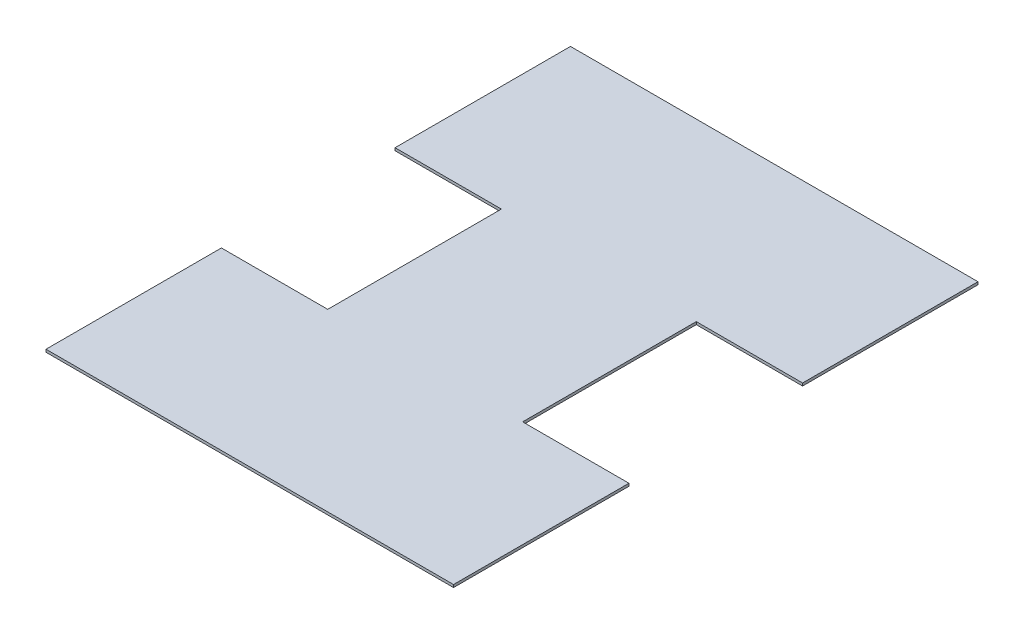
SolidWorks part; units mm, degrees
ref_plane "Front Plane" through (0, 0, 0) normal (0, 0, 1) x (1, 0, 0)
ref_plane "Top Plane" through (0, 0, 0) normal (0, 1, 0) x (1, 0, 0)
ref_plane "Right Plane" through (0, 0, 0) normal (1, 0, 0) x (0, 0, -1)
sketch "Sketch1" plane through (0, 0, 0) normal (0, 1, 0) x (1, 0, 0)
  line L0 (0, 296) -> (0, -296) construction
  line L1 (-230, -296) -> (230, -296)
  line L2 (-230, -296) -> (-230, -98)
  line L3 (-230, 296) -> (230, 296)
  line L4 (230, -296) -> (230, -98)
  line L5 (-230, -296) -> (230, 296) construction
  line L6 (-230, 296) -> (230, -296) construction
  line L7 (-230, 0) -> (230, 0) construction
  line L8 (-230, -98) -> (-110, -98)
  line L9 (-110, -98) -> (-110, 98)
  line L10 (-230, 98) -> (-110, 98)
  line L11 (230, -98) -> (110, -98)
  line L12 (110, -98) -> (110, 98)
  line L13 (230, 98) -> (110, 98)
  line L14 (230, 98) -> (230, 296)
  line L15 (-230, 98) -> (-230, 296)
  line L16 (230, 98) -> (230, -98) construction
  line L17 (-230, 98) -> (-230, -98) construction
  point P0 (0, 0)
  point P21 (-110, 0)
  dimension "D1" = 460
  dimension "D2" = 592
  dimension "D3" = 98
  dimension "D4" = 120
extrude "Boss-Extrude1" add sketch "Sketch1" along normal blind 3
sketch "Sketch2" plane through (0, 3, 0) normal (0, 1, 0) x (1, 0, 0)
  line L0 (188, -270) -> (200, -270) construction
  line L1 (188, -291) -> (200, -291) construction
  line L2 (188, -291) -> (188, -249) construction
  line L3 (188, -249) -> (200, -249) construction
  line L4 (200, -291) -> (200, -249) construction
  line L5 (188, -291) -> (200, -249) construction
  line L6 (188, -249) -> (200, -291) construction
  line L7 (0, 296) -> (0, -296) construction
  line L8 (230, 296) -> (-230, 296) construction
  line L9 (-230, -296) -> (230, -296) construction
  line L10 (-110, 0) -> (110, 0) construction
  line L11 (-110, 98) -> (-110, -98) construction
  line L12 (110, -98) -> (110, 98) construction
  line L13 (230, -296) -> (230, -98) construction
  line L14 (-188, -249) -> (-200, -291) construction
  line L15 (-188, -291) -> (-200, -249) construction
  line L16 (-200, -291) -> (-200, -249) construction
  line L17 (-188, -249) -> (-200, -249) construction
  line L18 (-188, -291) -> (-188, -249) construction
  line L19 (-188, -291) -> (-200, -291) construction
  line L20 (-188, -270) -> (-200, -270) construction
  line L21 (-188, 270) -> (-200, 270) construction
  line L22 (-188, 291) -> (-200, 291) construction
  line L23 (-188, 291) -> (-188, 249) construction
  line L24 (-188, 249) -> (-200, 249) construction
  line L25 (-200, 291) -> (-200, 249) construction
  line L26 (-188, 291) -> (-200, 249) construction
  line L27 (-188, 249) -> (-200, 291) construction
  line L28 (188, 249) -> (200, 291) construction
  line L29 (188, 291) -> (200, 249) construction
  line L30 (200, 291) -> (200, 249) construction
  line L31 (188, 249) -> (200, 249) construction
  line L32 (188, 291) -> (188, 249) construction
  line L33 (188, 291) -> (200, 291) construction
  line L34 (188, 270) -> (200, 270) construction
  line L35 (183.4, -233) -> (215, -233)
  line L36 (183.4, -233) -> (183.4, -103)
  line L37 (183.4, -103) -> (215, -103)
  line L38 (215, -233) -> (215, -103)
  line L39 (183.4, -233) -> (215, -103) construction
  line L40 (183.4, -103) -> (215, -233) construction
  line L41 (183.4, -168) -> (215, -168) construction
  line L42 (199.2, -103) -> (199.2, -233) construction
  line L43 (230, -98) -> (110, -98) construction
  line L44 (-199.2, -103) -> (-199.2, -233) construction
  line L45 (-183.4, -168) -> (-215, -168) construction
  line L46 (-183.4, -103) -> (-215, -233) construction
  line L47 (-183.4, -233) -> (-215, -103) construction
  line L48 (-215, -233) -> (-215, -103)
  line L49 (-183.4, -103) -> (-215, -103)
  line L50 (-183.4, -233) -> (-183.4, -103)
  line L51 (-183.4, -233) -> (-215, -233)
  line L52 (-183.4, 233) -> (-215, 103) construction
  line L53 (-183.4, 103) -> (-215, 233) construction
  line L54 (-183.4, 168) -> (-215, 168) construction
  line L55 (-199.2, 103) -> (-199.2, 233) construction
  line L56 (199.2, 103) -> (199.2, 233) construction
  line L57 (183.4, 168) -> (215, 168) construction
  line L58 (183.4, 103) -> (215, 233) construction
  line L59 (183.4, 233) -> (215, 103) construction
  line L60 (-183.4, 233) -> (-215, 233)
  line L61 (-183.4, 233) -> (-183.4, 103)
  line L62 (-183.4, 103) -> (-215, 103)
  line L63 (-215, 233) -> (-215, 103)
  line L64 (215, 233) -> (215, 103)
  line L65 (183.4, 103) -> (215, 103)
  line L66 (183.4, 233) -> (183.4, 103)
  line L67 (183.4, 233) -> (215, 233)
  circle A0 centre (194, -254) radius 2.55
  circle A1 centre (194, -286) radius 2.55
  circle A2 centre (-194, -286) radius 2.55
  circle A3 centre (-194, -254) radius 2.55
  circle A4 centre (-194, 254) radius 2.55
  circle A5 centre (-194, 286) radius 2.55
  circle A6 centre (194, 286) radius 2.55
  circle A7 centre (194, 254) radius 2.55
  circle A8 centre (210.2, -118) radius 2.05
  circle A9 centre (188.2, -118) radius 2.05
  circle A10 centre (188.2, -218) radius 2.05
  circle A11 centre (210.2, -218) radius 2.05
  circle A12 centre (-210.2, -218) radius 2.05
  circle A13 centre (-188.2, -218) radius 2.05
  circle A14 centre (-188.2, -118) radius 2.05
  circle A15 centre (-210.2, -118) radius 2.05
  circle A16 centre (-210.2, 118) radius 2.05
  circle A17 centre (-188.2, 118) radius 2.05
  circle A18 centre (-188.2, 218) radius 2.05
  circle A19 centre (-210.2, 218) radius 2.05
  circle A20 centre (210.2, 218) radius 2.05
  circle A21 centre (188.2, 218) radius 2.05
  circle A22 centre (188.2, 118) radius 2.05
  circle A23 centre (210.2, 118) radius 2.05
  point P0 (194, -270)
  point P9 (194, -249)
  point P26 (0, 0)
  point P27 (0, 0)
  point P28 (143.2319, -283.2644)
  point P39 (-194, -270)
  point P60 (-194, 270)
  point P61 (194, 270)
  point P62 (199.2, -168)
  point P97 (-199.2, -168)
  point P130 (-199.2, 168)
  point P131 (199.2, 168)
  dimension "D5" = 5.1
  dimension "D6" = 16
  dimension "D11" = 4.1
  dimension "D1" = 5
  dimension "D2" = 30
  dimension "D3" = 12
  dimension "D4" = 42
  dimension "D7" = 31.6
  dimension "D8" = 130
  dimension "D9" = 50
  dimension "D10" = 11
  dimension "D12" = 5
  dimension "D13" = 15
